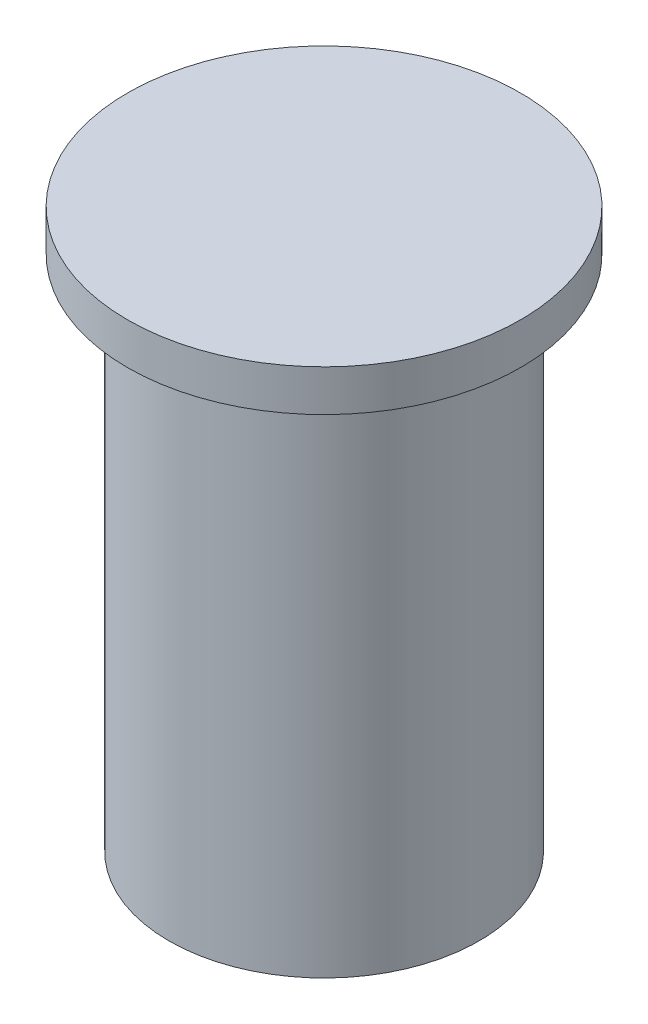
SolidWorks part; units mm, degrees
ref_plane "Front Plane" through (0, 0, 0) normal (0, 0, 1) x (1, 0, 0)
ref_plane "Top Plane" through (0, 0, 0) normal (0, 1, 0) x (1, 0, 0)
ref_plane "Right Plane" through (0, 0, 0) normal (1, 0, 0) x (0, 0, -1)
sketch "Sketch1" plane through (0, 0, 0) normal (1, 0, 0) x (0, 0, -1)
  line L0 (0, 0.4) -> (-1.9, 0.4)
  line L1 (0, 55) -> (0, -55) construction
  line L2 (-1.9, 0.4) -> (-1.9, 0)
  line L3 (-1.9, 0) -> (-1.5, 0)
  line L4 (-1.5, 0) -> (-1.5, -5)
  line L5 (-1.5, -5) -> (0, -5)
  line L6 (0, 0.4) -> (0, -5)
  line L7 (55, 0) -> (-55, 0) construction
  dimension "D1" = 1.5
  dimension "D2" = 1.9
  dimension "D3" = 0.4
  dimension "D4" = 5
revolve "Revolve1" add sketch "Sketch1" angle 360 about L6 region at (0, -2.2516, 0.7684)
